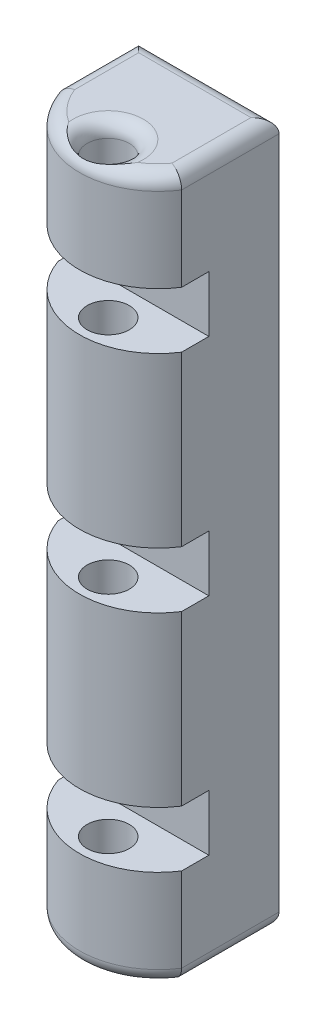
SolidWorks part; units mm, degrees
ref_plane "Front Plane" through (0, 0, 0) normal (0, 0, 1) x (1, 0, 0)
ref_plane "Top Plane" through (0, 0, 0) normal (0, 1, 0) x (1, 0, 0)
ref_plane "Right Plane" through (0, 0, 0) normal (1, 0, 0) x (0, 0, -1)
sketch "Sketch1" plane through (0, 0, 0) normal (0, 0, 1) x (1, 0, 0)
  line L1 (0, 0) -> (10, 0)
  line L2 (0, 0) -> (0, -50)
  line L3 (0, -50) -> (10, -50)
  line L4 (10, 0) -> (10, -50)
  dimension "D1" = 10
  dimension "D2" = 50
extrude "Boss-Extrude1" add sketch "Sketch1" along normal blind 20
sketch "Sketch2" plane through (0, 0, 20) normal (0, 0, 1) x (1, 0, 0)
  line L0 (10, -50) -> (10, 0) construction
  line L1 (0, 0) -> (10, 0)
  line L2 (0, 0) -> (0, -7)
  line L3 (0, -7) -> (10, -7)
  line L4 (10, 0) -> (10, -7)
  line L5 (0, 0) -> (0, -50) construction
  line L6 (0, -11) -> (10, -11)
  line L7 (0, -11) -> (0, -23)
  line L8 (0, -23) -> (10, -23)
  line L9 (10, -11) -> (10, -23)
  line L10 (0, -7) -> (0, -43)
  line L11 (0, -27) -> (10, -27)
  line L12 (0, -27) -> (0, -39)
  line L13 (0, -39) -> (10, -39)
  line L14 (10, -27) -> (10, -39)
  line L15 (0, -43) -> (10, -43)
  line L16 (0, -43) -> (0, -50)
  line L17 (0, -50) -> (10, -50)
  line L18 (10, -43) -> (10, -50)
  line L19 (10, -7) -> (10, -43)
  line M5 (0, 0) -> (0, -50)
  line M7 (10, -50) -> (10, 0)
  dimension "D1" = 7
  dimension "D2" = 4
  dimension "D3" = 12
  dimension "D4" = 4
  dimension "D5" = 12
  dimension "D6" = 4
extrude "Cut-Extrude1" cut sketch "Sketch2" against normal blind 5 contours L6 L3 M5 M7 | L11 L8 M5 M7 | L15 L13 M5 M7 region at (5, -9, 20) region at (5, -25, 20) region at (5, -41, 20)
sketch "Sketch3" plane through (10, 0, 0) normal (1, 0, 0) x (0, 0, -1)
  line L0 (-20, 0) -> (0, 0) construction
  line L1 (-10, 0) -> (0, 0)
  line L2 (-10, 0) -> (-10, -50)
  line L3 (-10, -50) -> (0, -50)
  line L4 (0, 0) -> (0, -50)
extrude "Cut-Extrude2" cut sketch "Sketch3" against normal blind 18
sketch "Sketch4" plane through (0, -39, 0) normal (0, -1, 0) x (1, 0, 0)
  circle A0 centre (5.261, 17.4265) radius 1.5
  dimension "D1" = 3
extrude "Cut-Extrude3" cut sketch "Sketch4" against normal through all both and the other way through all
sketch "Sketch5" plane through (0, -50, 0) normal (0, -1, 0) x (1, 0, 0)
  line L0 (0, 15.7376) -> (0, 20)
  line L1 (0, 20) -> (10, 20)
  line L2 (10, 20) -> (10, 16.9371)
  circle A0 centre (5.2925, 13.899) radius 5.6028
  line M3 (0, 20) -> (0, 10)
  line M5 (10, 10) -> (10, 20)
  line M6 (10, 20) -> (0, 20)
extrude "Cut-Extrude4" cut sketch "Sketch5" against normal through all both contours A0 M5 M6 M3 region at (0.1087, -50, 17.8688)
fillet "Fillet1" radius 1 10 edges at (10, -50, 13.4685) (5, -50, 10) (0, -50, 12.8688) (4.6252, -50, 19.4618) (5.261, -50, 15.9265) (0, 0, 12.8688) (5, 0, 10) (10, 0, 13.4685) (4.6252, 0, 19.4618) (5.261, 0, 15.9265)
